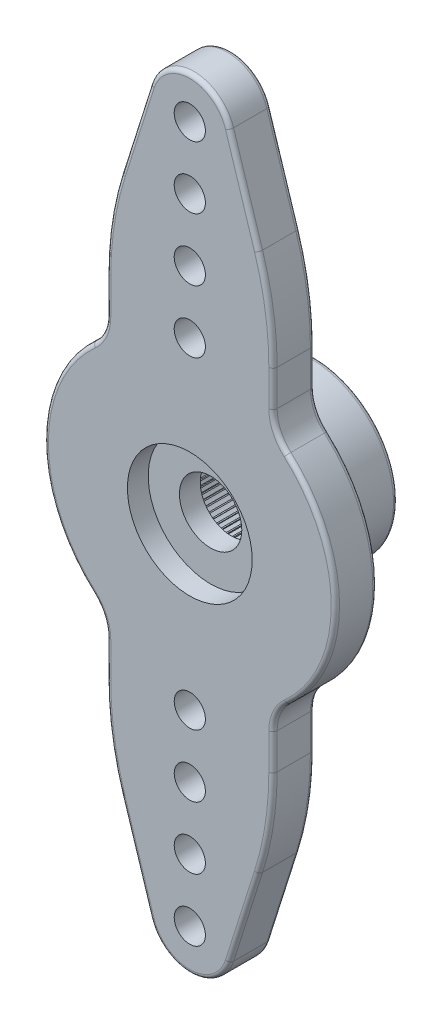
SolidWorks part; units mm, degrees
ref_plane "Ön Düzlem" through (0, 0, 0) normal (0, 0, 1) x (1, 0, 0)
ref_plane "Üst Düzlem" through (0, 0, 0) normal (0, 1, 0) x (1, 0, 0)
ref_plane "Sağ Düzlem" through (0, 0, 0) normal (1, 0, 0) x (0, 0, -1)
sketch "Sketch1" plane through (0, 0, 0) normal (0, 0, 1) x (1, 0, 0)
  line L0 (-4, 10.7446) -> (-4, 5.7446)
  line L1 (4, 10.7446) -> (4, 5.7446)
  line L2 (0, 0) -> (0, 16.75) construction
  line L3 (-4, 5.7446) -> (4, 5.7446) construction
  line L4 (-1.9067, 17.3539) -> (-4, 10.7446)
  line L5 (1.9067, 17.3539) -> (4, 10.7446)
  circle A0 centre (0, 0) radius 7
  circle A1 centre (0, 0) radius 18.75
  circle A2 centre (0, 16.75) radius 2
  circle A3 centre (0, 0) radius 1.5
  dimension "D1" = 37.5
  dimension "D2" = 14
  dimension "D3" = 4
  dimension "D5" = 3
  dimension "D4" = 5
  dimension "D6" = 8
extrude "Boss-Extrude1" add sketch "Sketch1" along normal blind 2 contours A0 A3 | A2 L4 L0 A0 L1 L5 | A2 region at (0, 10.6981, 0) region at (0, 6.802, 0) region at (0, 16.75, 0)
fillet "Fillet1" radius 15 2 edges at (-4, 10.7446, 1) (4, 10.7446, 1)
sketch "Sketch2" plane through (0, 0, 2) normal (0, 0, 1) x (1, 0, 0)
  line L0 (0, 0) -> (0, 18.75) construction
  arc A0 (1.9067, 17.3539) -> (-1.9067, 17.3539) centre (0, 16.75) ccw construction
  circle A1 centre (0, 16.75) radius 0.75
  circle A2 centre (0, 13.75) radius 0.75
  circle A3 centre (0, 10.75) radius 0.75
  circle A4 centre (0, 7.75) radius 0.75
  dimension "D1" = 1.5
  dimension "D2" = 2
  dimension "D3" = 4
extrude "Cut-Extrude1" cut sketch "Sketch2" against normal through all
pattern_circular "CirPattern2" count 2 over 360 about axis through (0, 0, 2) along (0, 0, 1) of "Boss-Extrude1", "Fillet1", "Cut-Extrude1"
fillet "Fillet2" radius 2 4 edges at (4, 5.7446, 1) (-4, 5.7446, 1) (-4, -5.7446, 1) (4, -5.7446, 1)
sketch "Sketch3" plane through (0, 0, 2) normal (0, 0, 1) x (1, 0, 0)
  circle A0 centre (0, 0) radius 3
  dimension "D1" = 6
extrude "Cut-Extrude2" cut sketch "Sketch3" against normal blind 1
sketch "Sketch4" plane through (0, 0, 0) normal (0, 0, -1) x (-1, 0, 0)
  circle A0 centre (0, 0) radius 4
  circle A1 centre (0, 0) radius 3
  dimension "D1" = 8
  dimension "D2" = 6
extrude "Boss-Extrude2" add sketch "Sketch4" along normal blind 4
sketch "Sketch5" plane through (0, 0, -4) normal (0, 0, -1) x (-1, 0, 0)
  line L0 (0, 0) -> (0, -4) construction
  line L2 (0.025, -2.8941) -> (-0.025, -2.8941)
  line L3 (0.025, -2.8941) -> (0.025, -3.3941)
  line L4 (0.025, -3.3941) -> (-0.025, -3.3941)
  line L5 (-0.025, -2.8941) -> (-0.025, -3.3941)
  line L6 (0.025, -2.8941) -> (-0.025, -3.3941) construction
  line L7 (0.025, -3.3941) -> (-0.025, -2.8941) construction
  circle A1 centre (0, 0) radius 4 construction
  point P0 (0, -3.1441)
  dimension "D1" = 0.05
  dimension "D2" = 0.5
extrude "Boss-Extrude3" add sketch "Sketch5" against normal up to surface (4 mm away) up to face at (-3, 0, 0)
pattern_circular "CirPattern3" count 80 over 360 about axis through (0, 0, -4) along (0, 0, -1) of "Boss-Extrude3"
fillet "Fillet3" radius 0.2 42 edges at (0, 18.75, 0) (-2.6033, 15.1545, 0) (-3.8239, 10.7173, 0) (-4, 7.567, 0) (-4.1743, 5.8917, 0) (-7, 0, 0) (-4.1743, -5.8917, 0) (-4, -7.567, 0) (-3.8239, -10.7173, 0) (-2.6033, -15.1545, 0) (0, -18.75, 0) (2.6033, -15.1545, 0) (3.8239, -10.7173, 0) (4, -7.567, 0) (4.1743, -5.8917, 0) (7, 0, 0) (4.1743, 5.8917, 0) (4, 7.567, 0) (3.8239, 10.7173, 0) (0, 18.75, 2) (-2.6033, 15.1545, 2) (-3.8239, 10.7173, 2) (-4, 7.567, 2) (-4.1743, 5.8917, 2) (-7, 0, 2) (-4.1743, -5.8917, 2) (-4, -7.567, 2) (-3.8239, -10.7173, 2) (-2.6033, -15.1545, 2) (0, -18.75, 2) (2.6033, -15.1545, 2) (3.8239, -10.7173, 2) (4, -7.567, 2) (4.1743, -5.8917, 2) (7, 0, 2) (4.1743, 5.8917, 2) (4, 7.567, 2) (3.8239, 10.7173, 2) (2.6033, 15.1545, 0) (2.6033, 15.1545, 2) (4, 0, 0) (-4, 0, -4)
